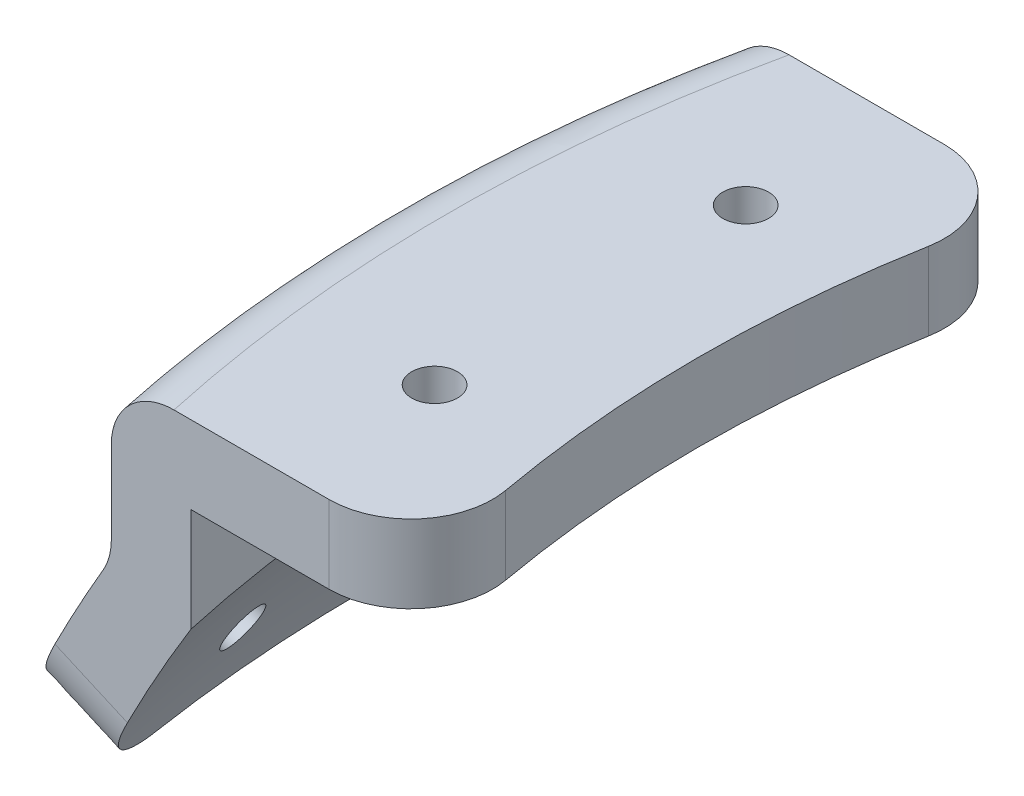
SolidWorks part; units mm, degrees
material "Polyether Polyol"
ref_plane "Front Plane" through (0, 0, 0) normal (0, 0, 1) x (1, 0, 0)
ref_plane "Top Plane" through (0, 0, 0) normal (0, 1, 0) x (1, 0, 0)
ref_plane "Right Plane" through (0, 0, 0) normal (1, 0, 0) x (0, 0, -1)
sketch "Sketch2" plane through (0, 0, 0) normal (0, 0, 1) x (1, 0, 0)
  line L0 (-194.3582, 176.3564) -> (-185.6556, 172.4846) construction
  line L1 (-183.6262, 216.8935) -> (-183.6262, 197.2811) construction
  line L2 (-174.1012, 207.3685) -> (-174.1012, 194.6685) construction
  line L3 (-145.5262, 207.3685) -> (-174.1012, 207.3685) construction
  line L4 (-145.5262, 207.3685) -> (-145.5262, 216.8935) construction
  line L5 (-145.5262, 216.8935) -> (-183.6262, 216.8935) construction
  line L6 (-194.3582, 176.3564) -> (-185.6556, 172.4846)
  line L7 (-183.6262, 216.8935) -> (-183.6262, 197.2811)
  line L8 (-174.1012, 207.3685) -> (-174.1012, 194.6685)
  line L9 (-145.5262, 207.3685) -> (-174.1012, 207.3685)
  line L10 (-145.5262, 207.3685) -> (-145.5262, 216.8935)
  line L11 (-145.5262, 216.8935) -> (-183.6262, 216.8935)
  line L12 (0, 0) -> (0, 215.8974) construction
  arc A0 (-183.6262, 197.2811) -> (-194.3582, 176.3564) centre (0, 89.8878) ccw construction
  arc A1 (-174.1012, 194.6685) -> (-185.6556, 172.4846) centre (0, 89.8878) ccw construction
  arc A2 (-183.6262, 197.2811) -> (-194.3582, 176.3564) centre (0, 89.8878) ccw
  arc A3 (-174.1012, 194.6685) -> (-185.6556, 172.4846) centre (0, 89.8878) ccw
revolve "Revolve1" add sketch "Sketch2" angle 30 mid plane about L12
fillet "Fillet1" radius 7.5 2 edges at (-183.6262, 197.2811, 0) (-183.6262, 216.8935, 0)
sketch "Sketch3" plane through (0, 207.3685, 0) normal (0, -1, 0) x (1, 0, 0)
  circle A0 centre (-158.75, 19.05) radius 3.5719 construction
  circle A1 centre (-158.75, -19.05) radius 3.5719 construction
  circle A2 centre (-158.75, 19.05) radius 3.5719 construction
  circle A3 centre (-158.75, -19.05) radius 3.5719 construction
  circle A4 centre (-158.75, -19.05) radius 2.805
  circle A5 centre (-158.75, 19.05) radius 2.805
  dimension "D1" = 5.61
extrude "Cut-Extrude1" cut sketch "Sketch3" against normal through all both and the other way through all
sketch "Sketch4" plane through (0, 216.8935, 0) normal (0, 1, 0) x (1, 0, 0)
  line L1 (-140.5675, 37.665) -> (-215.4275, 37.665)
  line L2 (-140.5675, 37.665) -> (-140.5675, -37.665)
  line L3 (-140.5675, -37.665) -> (-215.4275, -37.665)
  line L4 (-215.4275, 37.665) -> (-215.4275, -37.665)
extrude "Cut-Extrude2" cut sketch "Sketch4" against normal through all flip side to cut
fillet "Fillet2" radius 10 4 edges at (-140.5675, 212.131, -37.665) (-140.5675, 212.131, 37.665)
sketch "Sketch5" plane through (0, 0, 0) normal (0, 0, 1) x (1, 0, 0)
  line L0 (0, 89.8878) -> (-181.0525, 182.1386) construction
  line L1 (0, 0) -> (0, 215.8974) construction
  arc A1 (-174.1012, 194.6685) -> (-185.6556, 172.4846) centre (0, 89.8878) ccw construction
  dimension "D1" = 63
ref_plane "Plane1" through (36.3604, 71.3612, 0) normal (0.454, 0.891, 0) x (-0.891, 0.454, 0)
sketch "Sketch6" plane through (36.3604, 71.3612, 0) normal (0.454, 0.891, 0) x (-0.891, 0.454, 0)
  line L0 (216.8377, 18.9708) -> (270.6406, 23.678) construction
  line L1 (40.8082, 0) -> (244.0082, 0) construction
  line L2 (216.8377, 18.9708) -> (271.2422, 23.7306)
  line L3 (216.8377, 18.9708) -> (216.5932, 21.7652)
  line L4 (271.2422, 23.7306) -> (270.9977, 26.5249)
  line L5 (216.5932, 21.7652) -> (270.9977, 26.5249)
  dimension "D1" = 5
  dimension "D2" = 2.805
revolve "Cut-Revolve1" cut sketch "Sketch6" angle 360 about L0
mirror "Mirror1" about plane through (0, 0, 0) normal (0, 0, 1) of "Cut-Revolve1"
